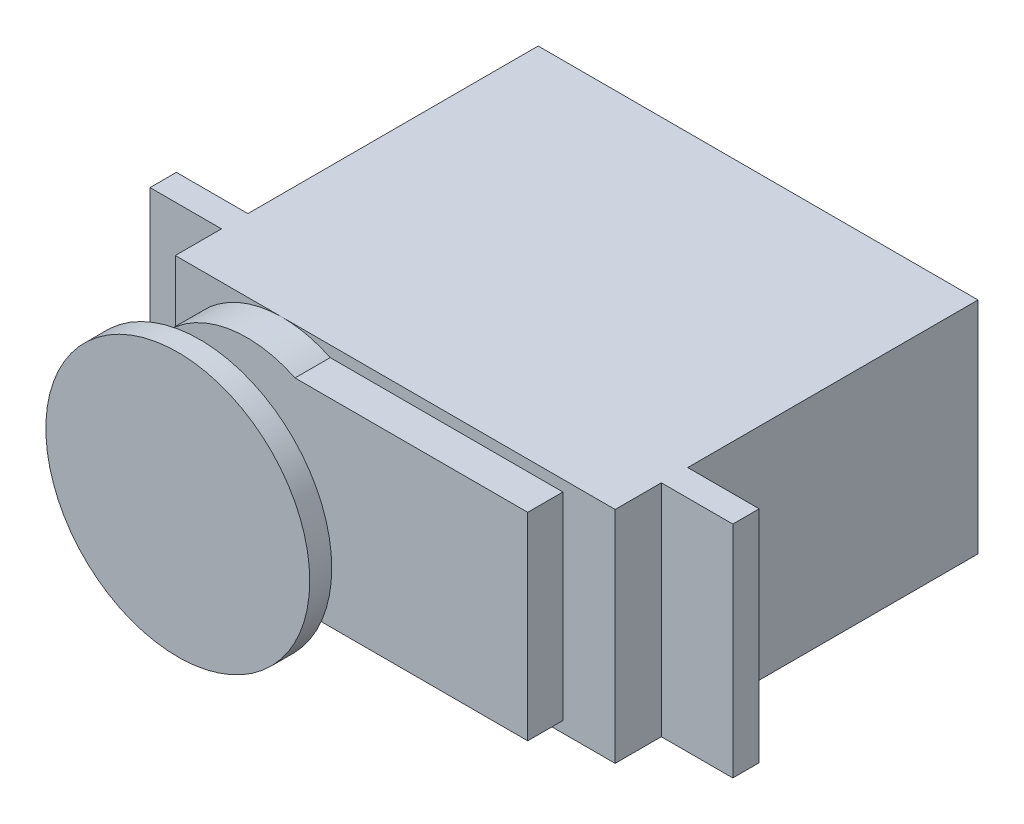
SolidWorks part; units mm, degrees
ref_plane "Front Plane" through (0, 0, 0) normal (0, 0, 1) x (1, 0, 0)
ref_plane "Top Plane" through (0, 0, 0) normal (0, 1, 0) x (1, 0, 0)
ref_plane "Right Plane" through (0, 0, 0) normal (1, 0, 0) x (0, 0, -1)
sketch "Sketch1" plane through (0, 0, 0) normal (0, 0, 1) x (1, 0, 0)
  line L1 (0, 0) -> (40, 0)
  line L2 (0, 0) -> (0, 20)
  line L3 (0, 20) -> (40, 20)
  line L4 (40, 0) -> (40, 20)
  dimension "D1" = 40
  dimension "D2" = 20
extrude "Boss-Extrude1" add sketch "Sketch1" along normal blind 33
sketch "Sketch3" plane through (40, 0, 0) normal (1, 0, 0) x (0, 0, -1)
  line L0 (-33, 20) -> (0, 20) construction
  line L1 (-28.8, 20) -> (-26.4, 20)
  line L2 (-28.8, 20) -> (-28.8, 0)
  line L3 (-28.8, 0) -> (-26.4, 0)
  line L4 (-26.4, 20) -> (-26.4, 0)
  line L5 (-33, 0) -> (0, 0) construction
  line L6 (-33, 0) -> (-33, 20) construction
  dimension "D1" = 2.4
  dimension "D2" = 4.2
extrude "Boss-Extrude2" add sketch "Sketch3" along normal blind 6.5
extrude "Boss-Extrude3" add sketch "Sketch3<2>" against normal blind 46.5
sketch "Sketch3<2>" plane through (40, 0, 0) normal (1, 0, 0) x (0, 0, -1) same geometry as "Sketch3"
sketch "Sketch4" plane through (0, 0, 33) normal (0, 0, 1) x (1, 0, 0)
  circle A0 centre (9.7264, 10) radius 5
extrude "Boss-Extrude4" add sketch "Sketch4" along normal blind 7.5
sketch "Sketch5" plane through (0, 0, 40.5) normal (0, 0, 1) x (1, 0, 0)
  circle A0 centre (9.7264, 10) radius 12
extrude "Boss-Extrude5" add sketch "Sketch5" along normal blind 2
sketch "Sketch6" plane through (0, 0, 33) normal (0, 0, 1) x (1, 0, 0)
  line L0 (0, 0) -> (40, 0) construction
  line L1 (40, 20) -> (0, 20) construction
  line L2 (40, 20) -> (40, 0) construction
  line L3 (35.25, 19) -> (14.0853, 19)
  line L4 (35.25, 19) -> (35.25, 1)
  line L5 (35.25, 1) -> (14.0853, 1)
  arc A0 (9.7264, 0) -> (9.7264, 20) centre (9.7264, 10) cw
  arc A1 (9.7264, 20) -> (14.0853, 1) centre (9.7264, 10) ccw
  arc A2 (9.7264, 20) -> (14.0853, 19) centre (9.7264, 10) cw
  line M1 (0, 20) -> (0, 0)
  circle M5 centre (9.7264, 10) radius 5
  dimension "D1" = 1
  dimension "D2" = 1
  dimension "D3" = 4.75
extrude "Boss-Extrude6" add sketch "Sketch6" along normal blind 3.2 contours A2 A0 A1 L5 L4 L3 M1 M5 region at (19.3297, 10, 33)
